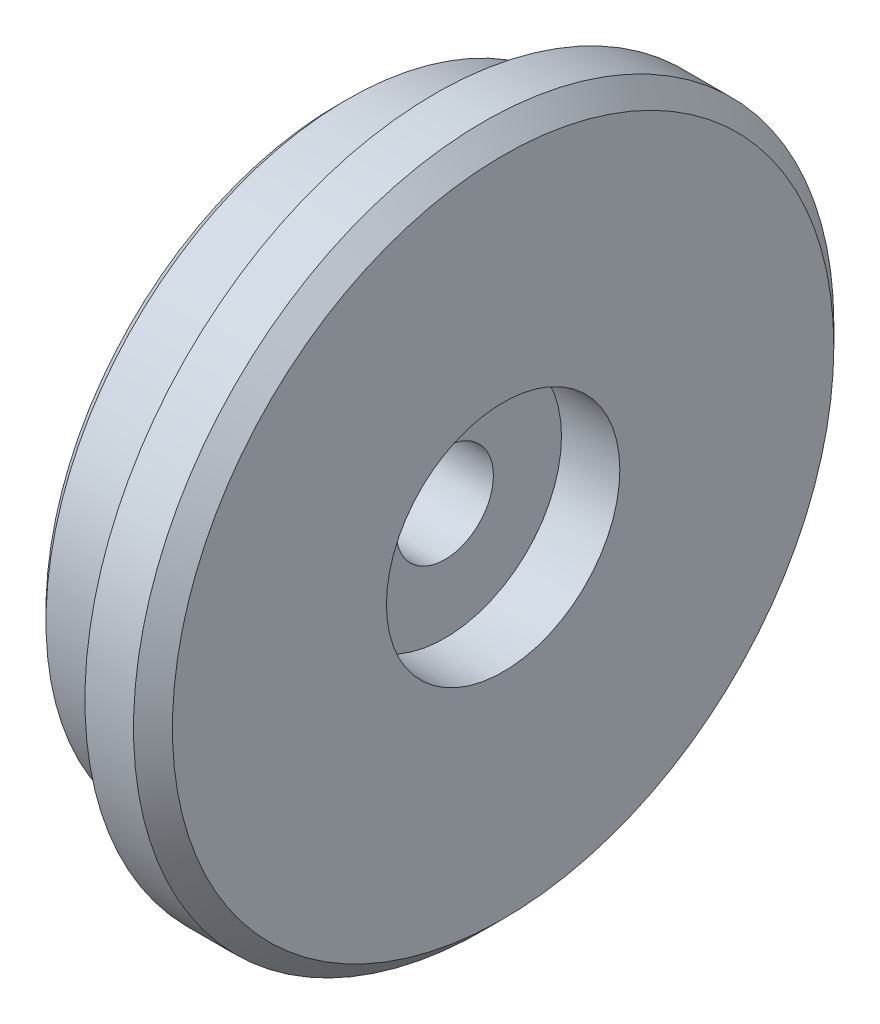
SolidWorks part; units mm, degrees
material "Alliage de zinc AC41A, brut"
ref_plane "Plan de face" through (0, 0, 0) normal (0, 0, 1) x (1, 0, 0)
ref_plane "Plan de dessus" through (0, 0, 0) normal (0, 1, 0) x (1, 0, 0)
ref_plane "Plan de droite" through (0, 0, 0) normal (1, 0, 0) x (0, 0, -1)
sketch "Esquisse1" plane through (0, 0, 0) normal (0, 0, 1) x (1, 0, 0)
  line L1 (0, 18) -> (-3.5, 18)
  line L2 (0, 18) -> (0, 6)
  line L3 (-3.5, 18) -> (-3.5, 15)
  line L4 (-3.5, 15) -> (-4.5, 15)
  line L5 (-4.5, 15) -> (-4.5, 15.5)
  line L6 (-4.5, 15.5) -> (-8, 15.5)
  line L8 (0, 6) -> (-3, 6)
  line L9 (-3, 6) -> (-3, 2.5)
  line L10 (-3, 2.5) -> (-8.5, 2.5)
  line L11 (-8, 15.5) -> (-8.5, 15)
  line L12 (-8.5, 2.5) -> (-8.5, 5)
  line L13 (-8.5, 5) -> (-5.75, 5)
  line L14 (-5, 5.75) -> (-5, 11.25)
  line L15 (-5.75, 12) -> (-8.5, 12)
  line L16 (-8.5, 12) -> (-8.5, 15)
  line L17 (-5, 11.25) -> (-5.75, 12)
  line L18 (-5.75, 5) -> (-5, 5.75)
  line L19 (0, 0) -> (-8.5, 0) construction
  line L20 (0, 0) -> (0, 6) construction
  point P13 (-5, 5)
  point P15 (-5, 12)
  dimension "D2" = 3.5
  dimension "D3" = 12
  dimension "D4" = 3
  dimension "D5" = 1
  dimension "D6" = 0.5
  dimension "D7" = 2.75
  dimension "D8" = 2.5
  dimension "D9" = 3
  dimension "D10" = 3.5
  dimension "D11" = 5.5
  dimension "D12" = 3.5
  dimension "D19" = 18
  dimension "D13" = 0.5
  dimension "D14" = 7
  dimension "D15" = 3
  dimension "D17" = 0.75
  dimension "D20" = 0.75
  dimension "D18" = 0.75
  dimension "D16" = 3.5
  dimension "D21" = 0.75
  dimension "D22" = 6
revolve "Révolution1789" add sketch "Esquisse1" angle 360 about L19
cosmetic thread "Représentation de filetage1" parameters "D2"=30
cosmetic thread "Représentation de filetage2" parameters "D2"=6
cosmetic thread "Cosmetic Thread1" parameters "D1"=5, "D2"=6
chamfer "Chamfer1" distance 1 angle 45 1 edges at (0, 0, -18)
